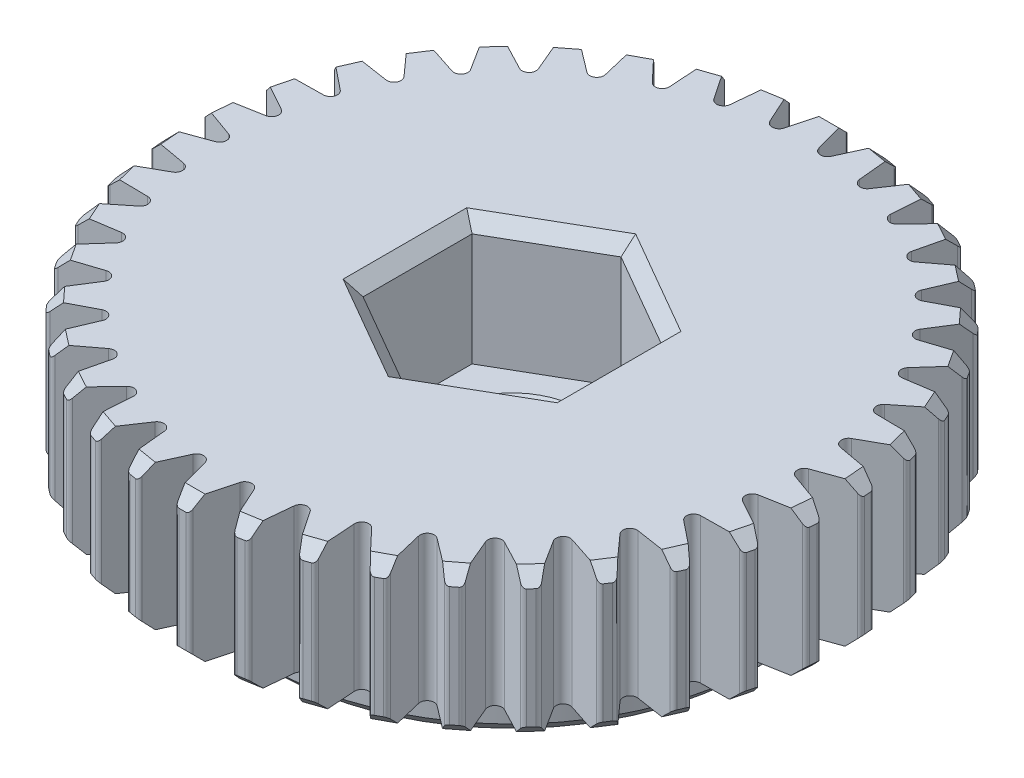
SolidWorks part; units mm, degrees
material "PET"
ref_plane "Front" through (0, 0, 0) normal (0, 0, 1) x (1, 0, 0)
ref_plane "Top" through (0, 0, 0) normal (0, 1, 0) x (1, 0, 0)
ref_plane "Right" through (0, 0, 0) normal (1, 0, 0) x (0, 0, -1)
sketch "Sketch1" plane through (0, 0, 0) normal (0, 1, 0) x (1, 0, 0)
  line L1 (-5.6833, 3.2812) -> (-5.6832, -3.2812)
  line L2 (-5.6832, -3.2812) -> (0, -6.5625)
  line L3 (0, -6.5625) -> (5.6833, -3.2812)
  line L4 (5.6833, -3.2812) -> (5.6832, 3.2812)
  line L5 (5.6832, 3.2812) -> (0, 6.5625)
  line L6 (0, 6.5625) -> (-5.6833, 3.2812)
  circle A0 centre (0, 0) radius 5.6833 construction
  circle A1 centre (0, 0) radius 17.4625
  dimension "D1" = 11.3665
  dimension "D2" = 34.925
extrude "Boss-Extrude1" add sketch "Sketch1" along normal blind 8.7312
ref_axis "Axis1" through (0, 50, 0) along (0, -1, 0)
sketch "Sketch2" plane through (0, 8.7312, 0) normal (0, 1, 0) x (1, 0, 0)
  line L0 (0, 0) -> (0, 17.4625) construction
  line L1 (0, 17.4625) -> (0, 19.8438) construction
  line L5 (-0.3969, 19.8438) -> (0.3969, 19.8438)
  line L6 (0.3969, 19.8438) -> (1.0433, 17.4313)
  line L7 (0, 17.4625) -> (1.0433, 17.4313)
  line L8 (0, 17.4625) -> (-1.0433, 17.4313)
  line L9 (-0.3969, 19.8438) -> (-1.0433, 17.4313)
  circle A0 centre (0, 0) radius 17.4625 construction
  dimension "D1" = 0.3969
  dimension "D2" = 2.3812
  dimension "D3" = 15
extrude "Boss-Extrude3" add sketch "Sketch2" against normal through all
chamfer "Chamfer3" distance 0.762 angle 45 2 edges at (0, 0, -19.8438) (0, 8.7312, -19.8438)
fillet "Fillet2" [suppressed] radius 0.762
fillet "Fillet3" radius 0.25 2 edges at (0.3969, 4.3656, -19.8438) (-0.3969, 4.3656, -19.8438)
pattern_circular "CirPattern2" count 38 over 360 about axis through (0, 8.7312, 0) along (0, 1, 0) of "Boss-Extrude3", "Fillet2", "Chamfer3", "Fillet3"
sketch "Sketch4" plane through (0, 8.7312, 0) normal (0, 1, 0) x (1, 0, 0)
  line L0 (1.0433, 17.4313) -> (0.6011, 19.0818) construction
  line L1 (2.5479, 18.9204) -> (1.84, 17.3653) construction
  circle A0 centre (1.4535, 17.5412) radius 0.4247
extrude "Cut-Extrude1" cut sketch "Sketch4" against normal through all
pattern_circular "CirPattern6" count 38 over 360 about axis through (0, 50, 0) along (0, -1, 0) of "Cut-Extrude1"
sketch "Sketch3" plane through (0, 0, 0) normal (0, -1, 0) x (1, 0, 0)
  line L6 (-5.6833, -3.2812) -> (0, -6.5625)
  line L7 (-5.6832, 3.2812) -> (-5.6833, -3.2812)
  line L8 (0, 6.5625) -> (-5.6832, 3.2812)
  line L9 (5.6833, 3.2812) -> (0, 6.5625)
  line L10 (5.6832, -3.2812) -> (5.6833, 3.2812)
  line L11 (0, -6.5625) -> (5.6832, -3.2812)
  line L12 (-5.6833, -3.2812) -> (0, -6.5625)
  line L13 (-5.6832, 3.2812) -> (-5.6833, -3.2812)
  line L14 (0, 6.5625) -> (-5.6832, 3.2812)
  line L15 (5.6833, 3.2812) -> (0, 6.5625)
  line L16 (5.6832, -3.2812) -> (5.6833, 3.2812)
  line L17 (0, -6.5625) -> (5.6832, -3.2812)
  circle A0 centre (0, 0) radius 15.113
  dimension "D1" = 30.226
  dimension "D2" = 0
extrude "Boss-Extrude4" add sketch "Sketch3" along normal blind 3.175
chamfer "Chamfer1" distance 0.762 angle 45 7 edges at (-5.6832, 8.7312, 0) (-2.8416, 8.7312, 4.9218) (2.8416, 8.7312, 4.9218) (5.6832, 8.7312, 0) (2.8416, 8.7312, -4.9218) (-2.8416, 8.7312, -4.9218) (0, -3.175, -15.113)
sketch "Sketch5" plane through (0, -3.175, 0) normal (0, -1, 0) x (1, 0, 0)
  line L7 (5.6832, -3.2812) -> (5.6833, 3.2812)
  line L8 (0, -6.5625) -> (5.6832, -3.2812)
  line L9 (-5.6832, -3.2812) -> (0, -6.5625)
  line L10 (-5.6832, 3.2812) -> (-5.6832, -3.2812)
  line L11 (0, 6.5625) -> (-5.6832, 3.2812)
  line L12 (5.6833, 3.2812) -> (0, 6.5625)
  line L13 (5.6832, -3.2812) -> (5.6833, 3.2812)
  line L14 (0, -6.5625) -> (5.6832, -3.2812)
  line L15 (-5.6832, -3.2812) -> (0, -6.5625)
  line L16 (-5.6832, 3.2812) -> (-5.6832, -3.2812)
  line L17 (0, 6.5625) -> (-5.6832, 3.2812)
  line L18 (5.6833, 3.2812) -> (0, 6.5625)
  dimension "D1" = 0
extrude "Boss-Extrude5" add sketch "Sketch5" against normal blind 4.3656
hole_wizard "1/4 Clearance Hole1" positions "Sketch6" profile "Sketch8" hole size "1/4" standard "ANSI Inch" end condition through all
sketch "Sketch6" plane through (0, -3.175, 0) normal (0, -1, 0) x (-1, 0, 0)
  point P0 (0, 0)
sketch "Sketch8" plane through (0, -3.175, 0) normal (1, 0, 0) x (0, 0, -1)
  line L0 (0, 0) -> (0, 4.3656)
  line L1 (0, 4.3656) -> (4.2062, 4.3656)
  line L2 (3.5712, 3.7306) -> (3.5712, 0.635)
  line L3 (3.5712, 0.635) -> (4.2062, 0)
  line L5 (4.2062, 0) -> (0, 0)
  line L6 (-3.5712, 0.635) -> (-4.2062, 0) construction
  line L7 (4.2062, 4.3656) -> (3.5712, 3.7306)
  line L8 (-4.2062, 4.3656) -> (-3.5712, 3.7306) construction
  line L11 (0, -6.35) -> (0, 107.95) construction
  dimension "Thru Hole Dia." = 7.1425
  dimension "Thru Hole Depth" = 4.3656
  dimension "Near C'Sink Dia." = 8.4125
  dimension "Near C'Sink Angle" = 90
  dimension "Far C'Sink Dia." = 8.4125
  dimension "Far C'Sink Angle" = 90
